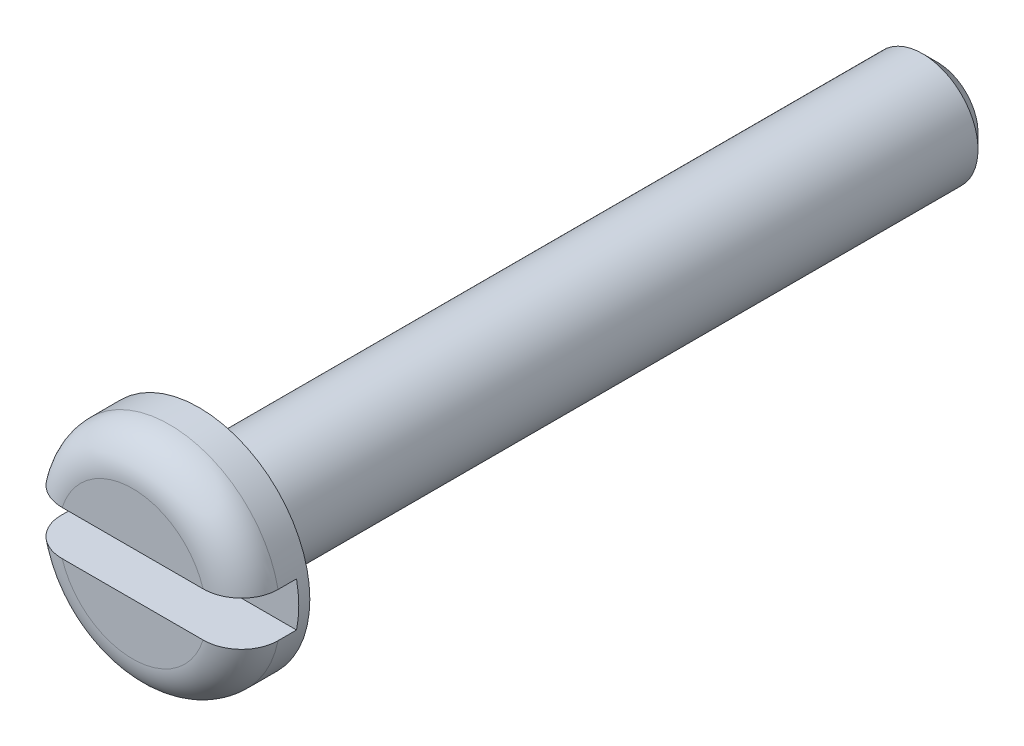
SolidWorks part; units mm, degrees
material "Простая углеродистая сталь"
ref_plane "Спереди" through (0, 0, 0) normal (0, 0, 1) x (1, 0, 0)
ref_plane "Сверху" through (0, 0, 0) normal (0, 1, 0) x (1, 0, 0)
ref_plane "Справа" through (0, 0, 0) normal (1, 0, 0) x (0, 0, -1)
sketch "Эскиз1" plane through (0, 0, 0) normal (0, 1, 0) x (1, 0, 0)
  line L0 (0, 0) -> (-3, 0)
  line L1 (-3, 0) -> (-3, 1.8)
  line L2 (-3, 1.8) -> (-1.5, 1.8)
  line L3 (-1.5, 1.8) -> (-1.5, 21.8)
  line L4 (-1.5, 21.8) -> (0, 21.8)
  line L5 (0, 21.8) -> (0, 0)
  dimension "D1" = 3
  dimension "D2" = 1.8
  dimension "D3" = 21.8
  dimension "D4" = 1.5
revolve "Повернуть1" add sketch "Эскиз1" angle 360 about L5
sketch "Эскиз2" plane through (0, 0, 0) normal (1, 0, 0) x (0, 0, -1)
  line L0 (0, 0) -> (22.6818, 0) construction
  line L1 (0, -0.6) -> (0, 0.6)
  line L2 (0, 0.6) -> (1.5, 0.6)
  line L3 (0, -0.6) -> (1.5, -0.6)
  line L4 (1.5, 0.6) -> (1.5, -0.6)
  point P7 (0, 0)
  point P10 (1.5, 0)
  dimension "D1" = 1.2
  dimension "D2" = 1.5
extrude "Вырез-Вытянуть1" cut sketch "Эскиз2" against normal through all both and the other way through all
chamfer "Фаска1" distance 0.4 angle 45 1 edges at (-1.5, 0, -21.8)
fillet "Скругление1" radius 1 2 edges at (0, -3, 0) (0, 3, 0)
fillet "Скругление2" radius 0.4 1 edges at (-1.5, 0, -1.8)
